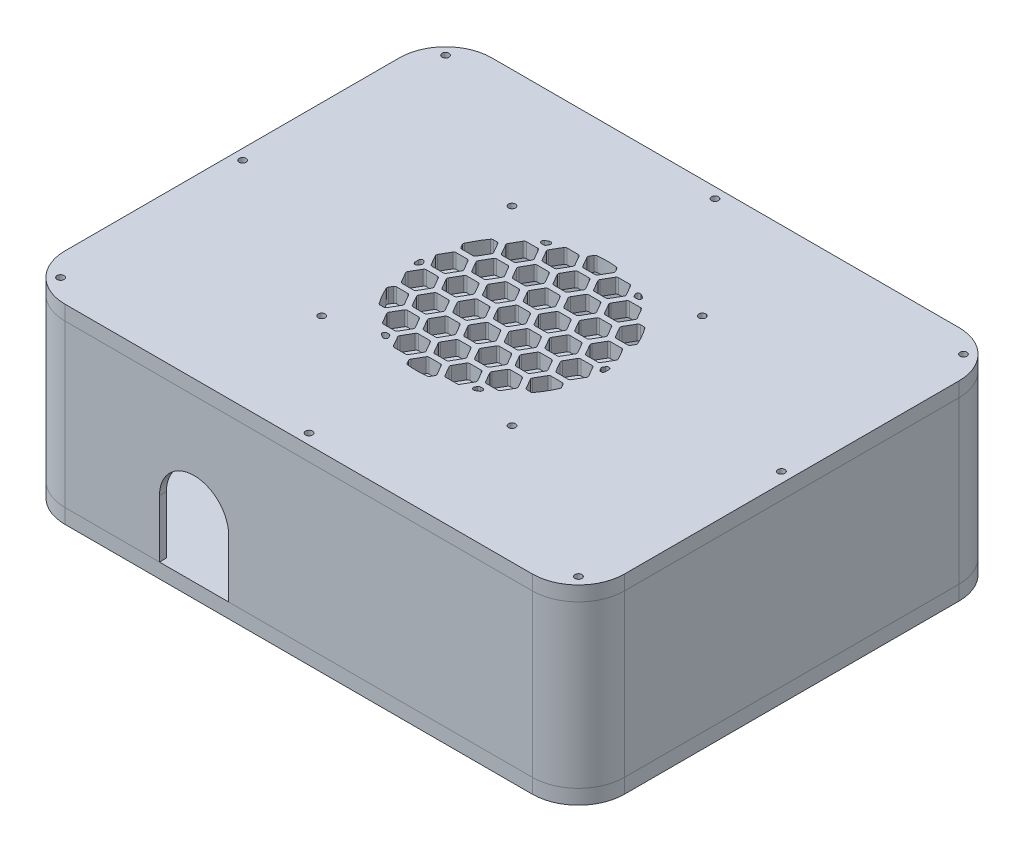
SolidWorks part; units mm, degrees
ref_plane "Front Plane" through (0, 0, 0) normal (0, 0, 1) x (1, 0, 0)
ref_plane "Top Plane" through (0, 0, 0) normal (0, 1, 0) x (1, 0, 0)
ref_plane "Right Plane" through (0, 0, 0) normal (1, 0, 0) x (0, 0, -1)
sketch "Sketch1" plane through (0, 0, 0) normal (0, 1, 0) x (1, 0, 0)
  line L0 (0, 92.5) -> (242.6, 92.5) construction
  line L1 (0, 0) -> (242.6, 0)
  line L2 (0, 0) -> (0, 185)
  line L3 (0, 185) -> (242.6, 185)
  line L4 (242.6, 0) -> (242.6, 185)
  line L6 (89, 170) -> (165.6, 170) construction
  line L7 (89, 170) -> (89, 15) construction
  line L8 (89, 15) -> (165.6, 15) construction
  line L9 (165.6, 170) -> (165.6, 15) construction
  line L10 (15, 106) -> (84, 106) construction
  line L11 (15, 106) -> (15, 15) construction
  line L12 (15, 15) -> (84, 15) construction
  line L13 (84, 106) -> (84, 15) construction
  line L14 (170.6, 127) -> (230.6, 127) construction
  line L15 (170.6, 127) -> (170.6, 15) construction
  line L16 (170.6, 15) -> (230.6, 15) construction
  line L17 (230.6, 127) -> (230.6, 15) construction
  line L22 (15, 170) -> (84, 170) construction
  line L23 (15, 170) -> (15, 121) construction
  line L24 (15, 121) -> (84, 121) construction
  line L25 (84, 170) -> (84, 121) construction
  dimension "D1" = 76.6
  dimension "D2" = 155
  dimension "D3" = 69
  dimension "D4" = 91
  dimension "D5" = 60
  dimension "D6" = 112
  dimension "D7" = 15
  dimension "D8" = 5
  dimension "D9" = 5
  dimension "D10" = 12
  dimension "D11" = 15
  dimension "D12" = 15
  dimension "D13" = 15
extrude "Boss-Extrude1" add sketch "Sketch1" along normal blind 6.35
fillet "Fillet1" radius 20 4 edges at (0, 3.175, -185) (242.6, 3.175, -185) (242.6, 3.175, 0) (0, 3.175, 0)
sketch "Sketch2" plane through (0, 6.35, 0) normal (0, 1, 0) x (1, 0, 0)
  line L0 (89, 170) -> (165.6, 170) construction
  line L1 (92.6, 167) -> (162, 167) construction
  line L2 (92.6, 167) -> (92.6, 25) construction
  line L3 (92.6, 25) -> (162, 25) construction
  line L4 (162, 167) -> (162, 25) construction
  line L5 (170.6, 127) -> (230.6, 127) construction
  line L6 (175.6, 70) -> (225.6, 70) construction
  line L7 (175.6, 70) -> (175.6, 45) construction
  line L8 (175.6, 45) -> (225.6, 45) construction
  line L9 (225.6, 70) -> (225.6, 45) construction
  line L10 (170.6, 15) -> (230.6, 15) construction
  line L11 (15, 170) -> (15, 121) construction
  line L12 (80.996, 125.18) -> (18.004, 125.18) construction
  line L13 (80.996, 125.18) -> (80.996, 165.82) construction
  line L14 (80.996, 165.82) -> (18.004, 165.82) construction
  line L15 (18.004, 125.18) -> (18.004, 165.82) construction
  line L16 (80.996, 125.18) -> (18.004, 165.82) construction
  line L17 (80.996, 165.82) -> (18.004, 125.18) construction
  line L18 (15, 170) -> (84, 170) construction
  circle A0 centre (92.6, 167) radius 1.5
  circle A1 centre (92.6, 25) radius 1.5
  circle A2 centre (162, 25) radius 1.5
  circle A3 centre (162, 167) radius 1.5
  circle A4 centre (175.6, 70) radius 1.5
  circle A5 centre (175.6, 45) radius 1.5
  circle A6 centre (225.6, 70) radius 1.5
  circle A7 centre (225.6, 45) radius 1.5
  circle A8 centre (18.004, 165.82) radius 1.5
  circle A9 centre (80.996, 165.82) radius 1.5
  circle A10 centre (80.996, 125.18) radius 1.5
  circle A11 centre (18.004, 125.18) radius 1.5
  point P6 (127.3, 167)
  point P7 (127.3, 170)
  point P20 (200.6, 70)
  point P23 (200.6, 127)
  point P26 (49.5, 145.5)
  point P34 (15, 145.5)
  point P37 (49.5, 170)
  dimension "D6" = 3
  dimension "D1" = 69.4
  dimension "D2" = 142
  dimension "D3" = 3
  dimension "D4" = 50
  dimension "D5" = 25
  dimension "D7" = 30
  dimension "D8" = 62.992
  dimension "D9" = 40.64
extrude "Cut-Extrude1" cut sketch "Sketch2" against normal through all
sketch "Sketch3" plane through (0, 6.35, 0) normal (0, 1, 0) x (1, 0, 0)
  line L21 (20, 20) -> (9.0398, 9.0398) construction
  line L22 (0, 165) -> (0, 20) construction
  line L23 (6.9185, 11.1612) -> (6.0465, 10.2892)
  line L24 (11.1612, 6.9185) -> (10.2892, 6.0465)
  line L25 (0, 92.5) -> (242.6, 92.5) construction
  line L26 (121.3, 185) -> (121.3, 0) construction
  line L27 (231.4388, 6.9185) -> (232.3108, 6.0465)
  line L28 (235.6815, 11.1612) -> (236.5535, 10.2892)
  line L29 (235.6815, 173.8388) -> (236.5535, 174.7108)
  line L30 (231.4388, 178.0815) -> (232.3108, 178.9535)
  line L31 (11.1612, 178.0815) -> (10.2892, 178.9535)
  line L32 (6.9185, 173.8388) -> (6.0465, 174.7108)
  line L33 (242.6, 20) -> (242.6, 165) construction
  line L34 (20, 0) -> (222.6, 0) construction
  line L35 (222.6, 185) -> (20, 185) construction
  line L36 (20, 20) -> (20, 12.5101) construction
  line L37 (3, 165) -> (3, 20)
  line L38 (20, 3) -> (222.6, 3)
  line L39 (239.6, 20) -> (239.6, 165)
  line L40 (222.6, 182) -> (20, 182)
  line L41 (222.6, 185) -> (20, 185)
  line L42 (0, 165) -> (0, 20)
  line L43 (20, 0) -> (222.6, 0)
  line L44 (242.6, 20) -> (242.6, 165)
  line L45 (222.6, 185) -> (20, 185)
  line L46 (0, 165) -> (0, 20)
  line L47 (20, 0) -> (222.6, 0)
  line L48 (242.6, 20) -> (242.6, 165)
  line L49 (4.5, 95.5) -> (3, 95.5)
  line L50 (3, 95.5) -> (3, 89.5)
  line L51 (3, 89.5) -> (4.5, 89.5)
  line L52 (239.6, 95.5) -> (239.6, 89.5)
  line L53 (238.1, 95.5) -> (239.6, 95.5)
  line L54 (239.6, 89.5) -> (238.1, 89.5)
  line L55 (118.3, 180.5) -> (118.3, 182)
  line L56 (124.3, 180.5) -> (124.3, 182)
  line L57 (118.3, 182) -> (124.3, 182)
  line L58 (118.3, 4.5) -> (118.3, 3)
  line L59 (124.3, 4.5) -> (124.3, 3)
  line L60 (118.3, 3) -> (124.3, 3)
  arc A22 (10.2892, 178.9535) -> (6.0465, 174.7108) centre (20, 165) ccw
  arc A24 (6.0465, 10.2892) -> (10.2892, 6.0465) centre (20, 20) ccw
  arc A26 (232.3108, 6.0465) -> (236.5535, 10.2892) centre (222.6, 20) ccw
  arc A28 (236.5535, 174.7108) -> (232.3108, 178.9535) centre (222.6, 165) ccw
  arc A43 (11.1612, 6.9185) -> (6.9185, 11.1612) centre (9.0398, 9.0398) ccw
  circle A44 centre (9.0398, 9.0398) radius 1.5
  circle A45 centre (233.5602, 9.0398) radius 1.5
  arc A46 (231.4388, 6.9185) -> (235.6815, 11.1612) centre (233.5602, 9.0398) cw
  circle A47 centre (233.5602, 175.9602) radius 1.5
  arc A48 (231.4388, 178.0815) -> (235.6815, 173.8388) centre (233.5602, 175.9602) ccw
  circle A49 centre (9.0398, 175.9602) radius 1.5
  arc A50 (11.1612, 178.0815) -> (6.9185, 173.8388) centre (9.0398, 175.9602) cw
  arc A51 (222.6, 0) -> (242.6, 20) centre (222.6, 20) ccw construction
  arc A52 (0, 20) -> (20, 0) centre (20, 20) ccw construction
  arc A53 (242.6, 165) -> (222.6, 185) centre (222.6, 165) ccw construction
  arc A54 (20, 185) -> (0, 165) centre (20, 165) ccw construction
  arc A55 (3, 20) -> (20, 3) centre (20, 20) ccw
  arc A56 (222.6, 3) -> (239.6, 20) centre (222.6, 20) ccw
  arc A57 (239.6, 165) -> (222.6, 182) centre (222.6, 165) ccw
  arc A58 (20, 182) -> (3, 165) centre (20, 165) ccw
  arc A59 (20, 185) -> (0, 165) centre (20, 165) ccw
  arc A60 (0, 20) -> (20, 0) centre (20, 20) ccw
  arc A61 (222.6, 0) -> (242.6, 20) centre (222.6, 20) ccw
  arc A62 (242.6, 165) -> (222.6, 185) centre (222.6, 165) ccw
  arc A63 (20, 185) -> (0, 165) centre (20, 165) ccw
  arc A64 (0, 20) -> (20, 0) centre (20, 20) ccw
  arc A65 (222.6, 0) -> (242.6, 20) centre (222.6, 20) ccw
  arc A66 (242.6, 165) -> (222.6, 185) centre (222.6, 165) ccw
  arc A67 (4.5, 89.5) -> (4.5, 95.5) centre (4.5, 92.5) ccw
  circle A68 centre (4.5, 92.5) radius 1.5
  arc A69 (238.1, 89.5) -> (238.1, 95.5) centre (238.1, 92.5) cw
  circle A70 centre (238.1, 92.5) radius 1.5
  circle A71 centre (121.3, 180.5) radius 1.5
  arc A72 (118.3, 180.5) -> (124.3, 180.5) centre (121.3, 180.5) ccw
  circle A73 centre (121.3, 4.5) radius 1.5
  arc A74 (118.3, 4.5) -> (124.3, 4.5) centre (121.3, 4.5) cw
  line M50 (222.6, 185) -> (20, 185)
  arc M51 (20, 185) -> (0, 165) centre (20, 165) ccw
  line M52 (0, 165) -> (0, 20)
  arc M53 (0, 20) -> (20, 0) centre (20, 20) ccw
  line M54 (20, 0) -> (222.6, 0)
  arc M55 (222.6, 0) -> (242.6, 20) centre (222.6, 20) ccw
  line M56 (242.6, 20) -> (242.6, 165)
  arc M57 (242.6, 165) -> (222.6, 185) centre (222.6, 165) ccw
  dimension "D3" = 0
  dimension "D4" = 6
  dimension "D5" = 3
  dimension "D1" = 3
  dimension "D7" = 3
  dimension "D6" = 3
  dimension "D2" = 45
extrude "Boss-Extrude2" add sketch "Sketch3" along normal blind 70 separate body contours M57 M50 M51 M52 M53 M54 M55 M56 | A50 L31 A22 A49 L32 | L37 A68 L50 L51 A67 L49 | A24 A44 L24 A43 L23 | A46 L27 A26 A45 L28 | A74 L58 L38 A73 L60 L59 | L39 A70 L52 L53 A69 L54 | L30 A48 L29 A28 A47 | L55 A72 L56 L40 A71 L57 region at (11.1012, 6.35, -11.1012) region at (3.075, 6.35, -91) region at (118.375, 6.35, -3.75) region at (7.0266, 6.35, -175.8543) region at (231.9348, 6.35, -6.5425) region at (119.8, 6.35, -181.925) region at (238.85, 6.35, -89.575) region at (233.4543, 6.35, -177.9734) region at (236.5264, 6.35, -178.9264)
fillet "Fillet5" radius 2 16 edges at (10.2892, 41.35, -178.9535) (6.0465, 41.35, -174.7108) (3, 41.35, -95.5) (3, 41.35, -89.5) (6.0465, 41.35, -10.2892) (10.2892, 41.35, -6.0465) (118.3, 41.35, -3) (124.3, 41.35, -3) (232.3108, 41.35, -6.0465) (236.5535, 41.35, -10.2892) (239.6, 41.35, -89.5) (239.6, 41.35, -95.5) (232.3108, 41.35, -178.9535) (124.3, 41.35, -182) (118.3, 41.35, -182) (236.5535, 41.35, -174.7108)
sketch "Sketch4" plane through (0, 76.35, 0) normal (0, 1, 0) x (1, 0, 0)
  line L4 (0, 165) -> (0, 20)
  line L5 (222.6, 185) -> (20, 185)
  line L6 (242.6, 20) -> (242.6, 165)
  line L7 (20, 0) -> (222.6, 0)
  line L8 (0, 165) -> (0, 20)
  line L9 (222.6, 185) -> (20, 185)
  line L10 (242.6, 20) -> (242.6, 165)
  line L11 (20, 0) -> (222.6, 0)
  arc A4 (20, 185) -> (0, 165) centre (20, 165) ccw
  arc A5 (242.6, 165) -> (222.6, 185) centre (222.6, 165) ccw
  arc A6 (222.6, 0) -> (242.6, 20) centre (222.6, 20) ccw
  arc A7 (0, 20) -> (20, 0) centre (20, 20) ccw
  arc A8 (20, 185) -> (0, 165) centre (20, 165) ccw
  arc A9 (242.6, 165) -> (222.6, 185) centre (222.6, 165) ccw
  arc A10 (222.6, 0) -> (242.6, 20) centre (222.6, 20) ccw
  arc A11 (0, 20) -> (20, 0) centre (20, 20) ccw
  dimension "D1" = 0
extrude "Boss-Extrude4" add sketch "Sketch4" along normal blind 6.35 separate body
sketch "Sketch5" plane through (0, 82.7, 0) normal (0, 1, 0) x (1, 0, 0)
  line L1 (80.05, 133.75) -> (162.55, 133.75) construction
  line L2 (80.05, 133.75) -> (80.05, 51.25) construction
  line L3 (80.05, 51.25) -> (162.55, 51.25) construction
  line L4 (162.55, 133.75) -> (162.55, 51.25) construction
  line L5 (80.05, 133.75) -> (162.55, 51.25) construction
  line L6 (80.05, 51.25) -> (162.55, 133.75) construction
  line L8 (222.6, 185) -> (20, 185) construction
  line L9 (0, 165) -> (0, 20) construction
  circle A0 centre (80.05, 133.75) radius 1.5
  circle A1 centre (80.05, 51.25) radius 1.5
  circle A2 centre (162.55, 51.25) radius 1.5
  circle A3 centre (162.55, 133.75) radius 1.5
  point P0 (121.3, 92.5)
  point P11 (121.3, 185)
  point P12 (0, 92.5)
  dimension "D2" = 3
  dimension "D1" = 82.5
extrude "Cut-Extrude2" cut sketch "Sketch5" against normal through all
sketch "Sketch6" plane through (0, 82.7, 0) normal (0, 1, 0) x (1, 0, 0)
  circle A20 centre (121.3, 4.5) radius 1.5 construction
  circle A21 centre (233.5602, 9.0398) radius 1.5 construction
  circle A22 centre (238.1, 92.5) radius 1.5 construction
  circle A23 centre (233.5602, 175.9602) radius 1.5 construction
  circle A24 centre (121.3, 180.5) radius 1.5 construction
  circle A25 centre (9.0398, 175.9602) radius 1.5 construction
  circle A26 centre (4.5, 92.5) radius 1.5 construction
  circle A27 centre (9.0398, 9.0398) radius 1.5 construction
  circle A28 centre (121.3, 4.5) radius 1.5
  circle A29 centre (233.5602, 9.0398) radius 1.5
  circle A30 centre (238.1, 92.5) radius 1.5
  circle A31 centre (233.5602, 175.9602) radius 1.5
  circle A32 centre (121.3, 180.5) radius 1.5
  circle A33 centre (9.0398, 175.9602) radius 1.5
  circle A34 centre (4.5, 92.5) radius 1.5
  circle A35 centre (9.0398, 9.0398) radius 1.5
extrude "Cut-Extrude3" cut sketch "Sketch6" against normal through all
sketch "Sketch7" plane through (0, 82.7, 0) normal (0, 1, 0) x (1, 0, 0)
  line L0 (80.05, 133.75) -> (162.55, 133.75) construction
  line L1 (80.05, 133.75) -> (80.05, 51.25) construction
  line L2 (80.05, 51.25) -> (162.55, 51.25) construction
  line L3 (162.55, 133.75) -> (162.55, 51.25) construction
  line L4 (80.05, 133.75) -> (162.55, 133.75) construction
  line L5 (80.05, 133.75) -> (80.05, 51.25) construction
  line L6 (80.05, 51.25) -> (162.55, 51.25) construction
  line L7 (162.55, 133.75) -> (162.55, 51.25) construction
  line L8 (157.7952, 117.0346) -> (151.7952, 117.0346)
  line L9 (124.3, 97.6962) -> (118.3, 97.6962)
  line L10 (118.3, 97.6962) -> (115.3, 92.5)
  line L11 (115.3, 92.5) -> (118.3, 87.3038)
  line L12 (118.3, 87.3038) -> (124.3, 87.3038)
  line L13 (124.3, 87.3038) -> (127.3, 92.5)
  line L14 (127.3, 92.5) -> (124.3, 97.6962)
  line L15 (138.4651, 98.9462) -> (135.4651, 104.1423)
  line L16 (135.4651, 104.1423) -> (129.4651, 104.1423)
  line L17 (129.4651, 104.1423) -> (126.4651, 98.9462)
  line L18 (126.4651, 98.9462) -> (129.4651, 93.75)
  line L19 (129.4651, 93.75) -> (135.4651, 93.75)
  line L20 (135.4651, 93.75) -> (138.4651, 98.9462)
  line L21 (127.3, 105.3923) -> (124.3, 110.5885)
  line L22 (124.3, 110.5885) -> (118.3, 110.5885)
  line L23 (118.3, 110.5885) -> (115.3, 105.3923)
  line L24 (115.3, 105.3923) -> (118.3, 100.1962)
  line L25 (118.3, 100.1962) -> (124.3, 100.1962)
  line L26 (124.3, 100.1962) -> (127.3, 105.3923)
  line L27 (135.4651, 117.0346) -> (129.4651, 117.0346)
  line L28 (129.4651, 117.0346) -> (126.4651, 111.8385)
  line L29 (126.4651, 111.8385) -> (129.4651, 106.6423)
  line L30 (129.4651, 106.6423) -> (135.4651, 106.6423)
  line L31 (135.4651, 106.6423) -> (138.4651, 111.8385)
  line L32 (138.4651, 111.8385) -> (135.4651, 117.0346)
  line L33 (151.7952, 117.0346) -> (148.7952, 111.8385)
  line L34 (148.7952, 111.8385) -> (151.7952, 106.6423)
  line L35 (151.7952, 106.6423) -> (157.7952, 106.6423)
  line L36 (157.7952, 106.6423) -> (160.7952, 111.8385)
  line L37 (160.7952, 111.8385) -> (157.7952, 117.0346)
  line L38 (149.6301, 105.3923) -> (146.6301, 110.5885)
  line L39 (146.6301, 110.5885) -> (140.6301, 110.5885)
  line L40 (140.6301, 110.5885) -> (137.6301, 105.3923)
  line L41 (137.6301, 105.3923) -> (140.6301, 100.1962)
  line L42 (140.6301, 100.1962) -> (146.6301, 100.1962)
  line L43 (146.6301, 100.1962) -> (149.6301, 105.3923)
  line L44 (146.6301, 97.6962) -> (140.6301, 97.6962)
  line L45 (140.6301, 97.6962) -> (137.6301, 92.5)
  line L46 (137.6301, 92.5) -> (140.6301, 87.3038)
  line L47 (140.6301, 87.3038) -> (146.6301, 87.3038)
  line L48 (146.6301, 87.3038) -> (149.6301, 92.5)
  line L49 (149.6301, 92.5) -> (146.6301, 97.6962)
  line L50 (160.7952, 98.9462) -> (157.7952, 104.1423)
  line L51 (157.7952, 104.1423) -> (151.7952, 104.1423)
  line L52 (151.7952, 104.1423) -> (148.7952, 98.9462)
  line L53 (148.7952, 98.9462) -> (151.7952, 93.75)
  line L54 (151.7952, 93.75) -> (157.7952, 93.75)
  line L55 (157.7952, 93.75) -> (160.7952, 98.9462)
  line L56 (180.1253, 117.0346) -> (174.1253, 117.0346)
  line L57 (174.1253, 117.0346) -> (171.1253, 111.8385)
  line L58 (171.1253, 111.8385) -> (174.1253, 106.6423)
  line L59 (174.1253, 106.6423) -> (180.1253, 106.6423)
  line L60 (180.1253, 106.6423) -> (183.1253, 111.8385)
  line L61 (183.1253, 111.8385) -> (180.1253, 117.0346)
  line L62 (171.9603, 105.3923) -> (168.9603, 110.5885)
  line L63 (168.9603, 110.5885) -> (162.9603, 110.5885)
  line L64 (162.9603, 110.5885) -> (159.9603, 105.3923)
  line L65 (159.9603, 105.3923) -> (162.9603, 100.1962)
  line L66 (162.9603, 100.1962) -> (168.9603, 100.1962)
  line L67 (168.9603, 100.1962) -> (171.9603, 105.3923)
  line L68 (168.9603, 97.6962) -> (162.9603, 97.6962)
  line L69 (162.9603, 97.6962) -> (159.9603, 92.5)
  line L70 (159.9603, 92.5) -> (162.9603, 87.3038)
  line L71 (162.9603, 87.3038) -> (168.9603, 87.3038)
  line L72 (168.9603, 87.3038) -> (171.9603, 92.5)
  line L73 (171.9603, 92.5) -> (168.9603, 97.6962)
  line L74 (183.1253, 98.9462) -> (180.1253, 104.1423)
  line L75 (180.1253, 104.1423) -> (174.1253, 104.1423)
  line L76 (174.1253, 104.1423) -> (171.1253, 98.9462)
  line L77 (171.1253, 98.9462) -> (174.1253, 93.75)
  line L78 (174.1253, 93.75) -> (180.1253, 93.75)
  line L79 (180.1253, 93.75) -> (183.1253, 98.9462)
  line L80 (157.7952, 142.8192) -> (151.7952, 142.8192)
  line L81 (151.7952, 142.8192) -> (148.7952, 137.6231)
  line L82 (148.7952, 137.6231) -> (151.7952, 132.4269)
  line L83 (151.7952, 132.4269) -> (157.7952, 132.4269)
  line L84 (157.7952, 132.4269) -> (160.7952, 137.6231)
  line L85 (160.7952, 137.6231) -> (157.7952, 142.8192)
  line L86 (149.6301, 131.1769) -> (146.6301, 136.3731)
  line L87 (146.6301, 136.3731) -> (140.6301, 136.3731)
  line L88 (140.6301, 136.3731) -> (137.6301, 131.1769)
  line L89 (137.6301, 131.1769) -> (140.6301, 125.9808)
  line L90 (140.6301, 125.9808) -> (146.6301, 125.9808)
  line L91 (146.6301, 125.9808) -> (149.6301, 131.1769)
  line L92 (146.6301, 123.4808) -> (140.6301, 123.4808)
  line L93 (140.6301, 123.4808) -> (137.6301, 118.2846)
  line L94 (137.6301, 118.2846) -> (140.6301, 113.0885)
  line L95 (140.6301, 113.0885) -> (146.6301, 113.0885)
  line L96 (146.6301, 113.0885) -> (149.6301, 118.2846)
  line L97 (149.6301, 118.2846) -> (146.6301, 123.4808)
  line L98 (160.7952, 124.7308) -> (157.7952, 129.9269)
  line L99 (157.7952, 129.9269) -> (151.7952, 129.9269)
  line L100 (151.7952, 129.9269) -> (148.7952, 124.7308)
  line L101 (148.7952, 124.7308) -> (151.7952, 119.5346)
  line L102 (151.7952, 119.5346) -> (157.7952, 119.5346)
  line L103 (157.7952, 119.5346) -> (160.7952, 124.7308)
  line L104 (180.1253, 142.8192) -> (174.1253, 142.8192)
  line L105 (174.1253, 142.8192) -> (171.1253, 137.6231)
  line L106 (171.1253, 137.6231) -> (174.1253, 132.4269)
  line L107 (174.1253, 132.4269) -> (180.1253, 132.4269)
  line L108 (180.1253, 132.4269) -> (183.1253, 137.6231)
  line L109 (183.1253, 137.6231) -> (180.1253, 142.8192)
  line L110 (171.9603, 131.1769) -> (168.9603, 136.3731)
  line L111 (168.9603, 136.3731) -> (162.9603, 136.3731)
  line L112 (162.9603, 136.3731) -> (159.9603, 131.1769)
  line L113 (159.9603, 131.1769) -> (162.9603, 125.9808)
  line L114 (162.9603, 125.9808) -> (168.9603, 125.9808)
  line L115 (168.9603, 125.9808) -> (171.9603, 131.1769)
  line L116 (168.9603, 123.4808) -> (162.9603, 123.4808)
  line L117 (162.9603, 123.4808) -> (159.9603, 118.2846)
  line L118 (159.9603, 118.2846) -> (162.9603, 113.0885)
  line L119 (162.9603, 113.0885) -> (168.9603, 113.0885)
  line L120 (168.9603, 113.0885) -> (171.9603, 118.2846)
  line L121 (171.9603, 118.2846) -> (168.9603, 123.4808)
  line L122 (183.1253, 124.7308) -> (180.1253, 129.9269)
  line L123 (180.1253, 129.9269) -> (174.1253, 129.9269)
  line L124 (174.1253, 129.9269) -> (171.1253, 124.7308)
  line L125 (171.1253, 124.7308) -> (174.1253, 119.5346)
  line L126 (174.1253, 119.5346) -> (180.1253, 119.5346)
  line L127 (180.1253, 119.5346) -> (183.1253, 124.7308)
  line L128 (135.4651, 142.8192) -> (129.4651, 142.8192)
  line L129 (129.4651, 142.8192) -> (126.4651, 137.6231)
  line L130 (126.4651, 137.6231) -> (129.4651, 132.4269)
  line L131 (129.4651, 132.4269) -> (135.4651, 132.4269)
  line L132 (135.4651, 132.4269) -> (138.4651, 137.6231)
  line L133 (138.4651, 137.6231) -> (135.4651, 142.8192)
  line L134 (127.3, 131.1769) -> (124.3, 136.3731)
  line L135 (124.3, 136.3731) -> (118.3, 136.3731)
  line L136 (118.3, 136.3731) -> (115.3, 131.1769)
  line L137 (115.3, 131.1769) -> (118.3, 125.9808)
  line L138 (118.3, 125.9808) -> (124.3, 125.9808)
  line L139 (124.3, 125.9808) -> (127.3, 131.1769)
  line L140 (124.3, 123.4808) -> (118.3, 123.4808)
  line L141 (118.3, 123.4808) -> (115.3, 118.2846)
  line L142 (115.3, 118.2846) -> (118.3, 113.0885)
  line L143 (118.3, 113.0885) -> (124.3, 113.0885)
  line L144 (124.3, 113.0885) -> (127.3, 118.2846)
  line L145 (127.3, 118.2846) -> (124.3, 123.4808)
  line L146 (138.4651, 124.7308) -> (135.4651, 129.9269)
  line L147 (135.4651, 129.9269) -> (129.4651, 129.9269)
  line L148 (129.4651, 129.9269) -> (126.4651, 124.7308)
  line L149 (126.4651, 124.7308) -> (129.4651, 119.5346)
  line L150 (129.4651, 119.5346) -> (135.4651, 119.5346)
  line L151 (135.4651, 119.5346) -> (138.4651, 124.7308)
  line L152 (124.3, 84.8038) -> (118.3, 84.8038)
  line L153 (118.3, 84.8038) -> (115.3, 79.6077)
  line L154 (115.3, 79.6077) -> (118.3, 74.4115)
  line L155 (118.3, 74.4115) -> (124.3, 74.4115)
  line L156 (124.3, 74.4115) -> (127.3, 79.6077)
  line L157 (127.3, 79.6077) -> (124.3, 84.8038)
  line L158 (138.4651, 86.0538) -> (135.4651, 91.25)
  line L159 (135.4651, 91.25) -> (129.4651, 91.25)
  line L160 (129.4651, 91.25) -> (126.4651, 86.0538)
  line L161 (126.4651, 86.0538) -> (129.4651, 80.8577)
  line L162 (129.4651, 80.8577) -> (135.4651, 80.8577)
  line L163 (135.4651, 80.8577) -> (138.4651, 86.0538)
  line L164 (160.7952, 86.0538) -> (157.7952, 91.25)
  line L165 (157.7952, 91.25) -> (151.7952, 91.25)
  line L166 (151.7952, 91.25) -> (148.7952, 86.0538)
  line L167 (148.7952, 86.0538) -> (151.7952, 80.8577)
  line L168 (151.7952, 80.8577) -> (157.7952, 80.8577)
  line L169 (157.7952, 80.8577) -> (160.7952, 86.0538)
  line L170 (168.9603, 84.8038) -> (162.9603, 84.8038)
  line L171 (162.9603, 84.8038) -> (159.9603, 79.6077)
  line L172 (159.9603, 79.6077) -> (162.9603, 74.4115)
  line L173 (162.9603, 74.4115) -> (168.9603, 74.4115)
  line L174 (168.9603, 74.4115) -> (171.9603, 79.6077)
  line L175 (171.9603, 79.6077) -> (168.9603, 84.8038)
  line L176 (146.6301, 84.8038) -> (140.6301, 84.8038)
  line L177 (140.6301, 84.8038) -> (137.6301, 79.6077)
  line L178 (137.6301, 79.6077) -> (140.6301, 74.4115)
  line L179 (140.6301, 74.4115) -> (146.6301, 74.4115)
  line L180 (146.6301, 74.4115) -> (149.6301, 79.6077)
  line L181 (149.6301, 79.6077) -> (146.6301, 84.8038)
  line L182 (124.3, 71.9115) -> (118.3, 71.9115)
  line L183 (118.3, 71.9115) -> (115.3, 66.7154)
  line L184 (115.3, 66.7154) -> (118.3, 61.5192)
  line L185 (118.3, 61.5192) -> (124.3, 61.5192)
  line L186 (124.3, 61.5192) -> (127.3, 66.7154)
  line L187 (127.3, 66.7154) -> (124.3, 71.9115)
  line L188 (138.4651, 73.1615) -> (135.4651, 78.3577)
  line L189 (135.4651, 78.3577) -> (129.4651, 78.3577)
  line L190 (129.4651, 78.3577) -> (126.4651, 73.1615)
  line L191 (126.4651, 73.1615) -> (129.4651, 67.9654)
  line L192 (129.4651, 67.9654) -> (135.4651, 67.9654)
  line L193 (135.4651, 67.9654) -> (138.4651, 73.1615)
  line L194 (160.7952, 73.1615) -> (157.7952, 78.3577)
  line L195 (157.7952, 78.3577) -> (151.7952, 78.3577)
  line L196 (151.7952, 78.3577) -> (148.7952, 73.1615)
  line L197 (148.7952, 73.1615) -> (151.7952, 67.9654)
  line L198 (151.7952, 67.9654) -> (157.7952, 67.9654)
  line L199 (157.7952, 67.9654) -> (160.7952, 73.1615)
  line L200 (168.9603, 71.9115) -> (162.9603, 71.9115)
  line L201 (162.9603, 71.9115) -> (159.9603, 66.7154)
  line L202 (159.9603, 66.7154) -> (162.9603, 61.5192)
  line L203 (162.9603, 61.5192) -> (168.9603, 61.5192)
  line L204 (168.9603, 61.5192) -> (171.9603, 66.7154)
  line L205 (171.9603, 66.7154) -> (168.9603, 71.9115)
  line L206 (146.6301, 71.9115) -> (140.6301, 71.9115)
  line L207 (140.6301, 71.9115) -> (137.6301, 66.7154)
  line L208 (137.6301, 66.7154) -> (140.6301, 61.5192)
  line L209 (140.6301, 61.5192) -> (146.6301, 61.5192)
  line L210 (146.6301, 61.5192) -> (149.6301, 66.7154)
  line L211 (149.6301, 66.7154) -> (146.6301, 71.9115)
  line L212 (124.3, 59.0192) -> (118.3, 59.0192)
  line L213 (118.3, 59.0192) -> (115.3, 53.8231)
  line L214 (115.3, 53.8231) -> (118.3, 48.6269)
  line L215 (118.3, 48.6269) -> (124.3, 48.6269)
  line L216 (124.3, 48.6269) -> (127.3, 53.8231)
  line L217 (127.3, 53.8231) -> (124.3, 59.0192)
  line L218 (138.4651, 60.2692) -> (135.4651, 65.4654)
  line L219 (135.4651, 65.4654) -> (129.4651, 65.4654)
  line L220 (129.4651, 65.4654) -> (126.4651, 60.2692)
  line L221 (126.4651, 60.2692) -> (129.4651, 55.0731)
  line L222 (129.4651, 55.0731) -> (135.4651, 55.0731)
  line L223 (135.4651, 55.0731) -> (138.4651, 60.2692)
  line L224 (160.7952, 60.2692) -> (157.7952, 65.4654)
  line L225 (157.7952, 65.4654) -> (151.7952, 65.4654)
  line L226 (151.7952, 65.4654) -> (148.7952, 60.2692)
  line L227 (148.7952, 60.2692) -> (151.7952, 55.0731)
  line L228 (151.7952, 55.0731) -> (157.7952, 55.0731)
  line L229 (157.7952, 55.0731) -> (160.7952, 60.2692)
  line L230 (168.9603, 59.0192) -> (162.9603, 59.0192)
  line L231 (162.9603, 59.0192) -> (159.9603, 53.8231)
  line L232 (159.9603, 53.8231) -> (162.9603, 48.6269)
  line L233 (162.9603, 48.6269) -> (168.9603, 48.6269)
  line L234 (168.9603, 48.6269) -> (171.9603, 53.8231)
  line L235 (171.9603, 53.8231) -> (168.9603, 59.0192)
  line L236 (146.6301, 59.0192) -> (140.6301, 59.0192)
  line L237 (140.6301, 59.0192) -> (137.6301, 53.8231)
  line L238 (137.6301, 53.8231) -> (140.6301, 48.6269)
  line L239 (140.6301, 48.6269) -> (146.6301, 48.6269)
  line L240 (146.6301, 48.6269) -> (149.6301, 53.8231)
  line L241 (149.6301, 53.8231) -> (146.6301, 59.0192)
  line L242 (124.3, 46.1269) -> (118.3, 46.1269)
  line L243 (118.3, 46.1269) -> (115.3, 40.9308)
  line L244 (115.3, 40.9308) -> (118.3, 35.7346)
  line L245 (118.3, 35.7346) -> (124.3, 35.7346)
  line L246 (124.3, 35.7346) -> (127.3, 40.9308)
  line L247 (127.3, 40.9308) -> (124.3, 46.1269)
  line L248 (138.4651, 47.3769) -> (135.4651, 52.5731)
  line L249 (135.4651, 52.5731) -> (129.4651, 52.5731)
  line L250 (129.4651, 52.5731) -> (126.4651, 47.3769)
  line L251 (126.4651, 47.3769) -> (129.4651, 42.1808)
  line L252 (129.4651, 42.1808) -> (135.4651, 42.1808)
  line L253 (135.4651, 42.1808) -> (138.4651, 47.3769)
  line L254 (160.7952, 47.3769) -> (157.7952, 52.5731)
  line L255 (157.7952, 52.5731) -> (151.7952, 52.5731)
  line L256 (151.7952, 52.5731) -> (148.7952, 47.3769)
  line L257 (148.7952, 47.3769) -> (151.7952, 42.1808)
  line L258 (151.7952, 42.1808) -> (157.7952, 42.1808)
  line L259 (157.7952, 42.1808) -> (160.7952, 47.3769)
  line L260 (168.9603, 46.1269) -> (162.9603, 46.1269)
  line L261 (162.9603, 46.1269) -> (159.9603, 40.9308)
  line L262 (159.9603, 40.9308) -> (162.9603, 35.7346)
  line L263 (162.9603, 35.7346) -> (168.9603, 35.7346)
  line L264 (168.9603, 35.7346) -> (171.9603, 40.9308)
  line L265 (171.9603, 40.9308) -> (168.9603, 46.1269)
  line L266 (146.6301, 46.1269) -> (140.6301, 46.1269)
  line L267 (140.6301, 46.1269) -> (137.6301, 40.9308)
  line L268 (137.6301, 40.9308) -> (140.6301, 35.7346)
  line L269 (140.6301, 35.7346) -> (146.6301, 35.7346)
  line L270 (146.6301, 35.7346) -> (149.6301, 40.9308)
  line L271 (149.6301, 40.9308) -> (146.6301, 46.1269)
  line L272 (104.9699, 131.1769) -> (101.9699, 136.3731)
  line L273 (101.9699, 136.3731) -> (95.9699, 136.3731)
  line L274 (95.9699, 136.3731) -> (92.9699, 131.1769)
  line L275 (92.9699, 131.1769) -> (95.9699, 125.9808)
  line L276 (95.9699, 125.9808) -> (101.9699, 125.9808)
  line L277 (101.9699, 125.9808) -> (104.9699, 131.1769)
  line L278 (101.9699, 123.4808) -> (95.9699, 123.4808)
  line L279 (95.9699, 123.4808) -> (92.9699, 118.2846)
  line L280 (92.9699, 118.2846) -> (95.9699, 113.0885)
  line L281 (95.9699, 113.0885) -> (101.9699, 113.0885)
  line L282 (101.9699, 113.0885) -> (104.9699, 118.2846)
  line L283 (104.9699, 118.2846) -> (101.9699, 123.4808)
  line L284 (101.9699, 84.8038) -> (95.9699, 84.8038)
  line L285 (95.9699, 84.8038) -> (92.9699, 79.6077)
  line L286 (92.9699, 79.6077) -> (95.9699, 74.4115)
  line L287 (95.9699, 74.4115) -> (101.9699, 74.4115)
  line L288 (101.9699, 74.4115) -> (104.9699, 79.6077)
  line L289 (104.9699, 79.6077) -> (101.9699, 84.8038)
  line L290 (101.9699, 71.9115) -> (95.9699, 71.9115)
  line L291 (95.9699, 71.9115) -> (92.9699, 66.7154)
  line L292 (92.9699, 66.7154) -> (95.9699, 61.5192)
  line L293 (95.9699, 61.5192) -> (101.9699, 61.5192)
  line L294 (101.9699, 61.5192) -> (104.9699, 66.7154)
  line L295 (104.9699, 66.7154) -> (101.9699, 71.9115)
  line L296 (101.9699, 59.0192) -> (95.9699, 59.0192)
  line L297 (95.9699, 59.0192) -> (92.9699, 53.8231)
  line L298 (92.9699, 53.8231) -> (95.9699, 48.6269)
  line L299 (95.9699, 48.6269) -> (101.9699, 48.6269)
  line L300 (101.9699, 48.6269) -> (104.9699, 53.8231)
  line L301 (104.9699, 53.8231) -> (101.9699, 59.0192)
  line L302 (116.1349, 60.2692) -> (113.1349, 65.4654)
  line L303 (113.1349, 65.4654) -> (107.1349, 65.4654)
  line L304 (107.1349, 65.4654) -> (104.1349, 60.2692)
  line L305 (104.1349, 60.2692) -> (107.1349, 55.0731)
  line L306 (107.1349, 55.0731) -> (113.1349, 55.0731)
  line L307 (113.1349, 55.0731) -> (116.1349, 60.2692)
  line L308 (116.1349, 73.1615) -> (113.1349, 78.3577)
  line L309 (113.1349, 78.3577) -> (107.1349, 78.3577)
  line L310 (107.1349, 78.3577) -> (104.1349, 73.1615)
  line L311 (104.1349, 73.1615) -> (107.1349, 67.9654)
  line L312 (107.1349, 67.9654) -> (113.1349, 67.9654)
  line L313 (113.1349, 67.9654) -> (116.1349, 73.1615)
  line L314 (101.9699, 97.6962) -> (95.9699, 97.6962)
  line L315 (95.9699, 97.6962) -> (92.9699, 92.5)
  line L316 (92.9699, 92.5) -> (95.9699, 87.3038)
  line L317 (95.9699, 87.3038) -> (101.9699, 87.3038)
  line L318 (101.9699, 87.3038) -> (104.9699, 92.5)
  line L319 (104.9699, 92.5) -> (101.9699, 97.6962)
  line L320 (116.1349, 86.0538) -> (113.1349, 91.25)
  line L321 (113.1349, 91.25) -> (107.1349, 91.25)
  line L322 (107.1349, 91.25) -> (104.1349, 86.0538)
  line L323 (104.1349, 86.0538) -> (107.1349, 80.8577)
  line L324 (107.1349, 80.8577) -> (113.1349, 80.8577)
  line L325 (113.1349, 80.8577) -> (116.1349, 86.0538)
  line L326 (116.1349, 98.9462) -> (113.1349, 104.1423)
  line L327 (113.1349, 104.1423) -> (107.1349, 104.1423)
  line L328 (107.1349, 104.1423) -> (104.1349, 98.9462)
  line L329 (104.1349, 98.9462) -> (107.1349, 93.75)
  line L330 (107.1349, 93.75) -> (113.1349, 93.75)
  line L331 (113.1349, 93.75) -> (116.1349, 98.9462)
  line L332 (104.9699, 105.3923) -> (101.9699, 110.5885)
  line L333 (101.9699, 110.5885) -> (95.9699, 110.5885)
  line L334 (95.9699, 110.5885) -> (92.9699, 105.3923)
  line L335 (92.9699, 105.3923) -> (95.9699, 100.1962)
  line L336 (95.9699, 100.1962) -> (101.9699, 100.1962)
  line L337 (101.9699, 100.1962) -> (104.9699, 105.3923)
  line L338 (113.1349, 117.0346) -> (107.1349, 117.0346)
  line L339 (107.1349, 117.0346) -> (104.1349, 111.8385)
  line L340 (104.1349, 111.8385) -> (107.1349, 106.6423)
  line L341 (107.1349, 106.6423) -> (113.1349, 106.6423)
  line L342 (113.1349, 106.6423) -> (116.1349, 111.8385)
  line L343 (116.1349, 111.8385) -> (113.1349, 117.0346)
  line L344 (116.1349, 124.7308) -> (113.1349, 129.9269)
  line L345 (113.1349, 129.9269) -> (107.1349, 129.9269)
  line L346 (107.1349, 129.9269) -> (104.1349, 124.7308)
  line L347 (104.1349, 124.7308) -> (107.1349, 119.5346)
  line L348 (107.1349, 119.5346) -> (113.1349, 119.5346)
  line L349 (113.1349, 119.5346) -> (116.1349, 124.7308)
  line L350 (116.1349, 47.3769) -> (113.1349, 52.5731)
  line L351 (113.1349, 52.5731) -> (107.1349, 52.5731)
  line L352 (107.1349, 52.5731) -> (104.1349, 47.3769)
  line L353 (104.1349, 47.3769) -> (107.1349, 42.1808)
  line L354 (107.1349, 42.1808) -> (113.1349, 42.1808)
  line L355 (113.1349, 42.1808) -> (116.1349, 47.3769)
  line L356 (82.6397, 131.1769) -> (79.6397, 136.3731)
  line L357 (79.6397, 136.3731) -> (73.6397, 136.3731)
  line L358 (73.6397, 136.3731) -> (70.6397, 131.1769)
  line L359 (70.6397, 131.1769) -> (73.6397, 125.9808)
  line L360 (73.6397, 125.9808) -> (79.6397, 125.9808)
  line L361 (79.6397, 125.9808) -> (82.6397, 131.1769)
  line L362 (79.6397, 123.4808) -> (73.6397, 123.4808)
  line L363 (73.6397, 123.4808) -> (70.6397, 118.2846)
  line L364 (70.6397, 118.2846) -> (73.6397, 113.0885)
  line L365 (73.6397, 113.0885) -> (79.6397, 113.0885)
  line L366 (79.6397, 113.0885) -> (82.6397, 118.2846)
  line L367 (82.6397, 118.2846) -> (79.6397, 123.4808)
  line L368 (79.6397, 84.8038) -> (73.6397, 84.8038)
  line L369 (73.6397, 84.8038) -> (70.6397, 79.6077)
  line L370 (70.6397, 79.6077) -> (73.6397, 74.4115)
  line L371 (73.6397, 74.4115) -> (79.6397, 74.4115)
  line L372 (79.6397, 74.4115) -> (82.6397, 79.6077)
  line L373 (82.6397, 79.6077) -> (79.6397, 84.8038)
  line L374 (79.6397, 71.9115) -> (73.6397, 71.9115)
  line L375 (73.6397, 71.9115) -> (70.6397, 66.7154)
  line L376 (70.6397, 66.7154) -> (73.6397, 61.5192)
  line L377 (73.6397, 61.5192) -> (79.6397, 61.5192)
  line L378 (79.6397, 61.5192) -> (82.6397, 66.7154)
  line L379 (82.6397, 66.7154) -> (79.6397, 71.9115)
  line L380 (79.6397, 59.0192) -> (73.6397, 59.0192)
  line L381 (73.6397, 59.0192) -> (70.6397, 53.8231)
  line L382 (70.6397, 53.8231) -> (73.6397, 48.6269)
  line L383 (73.6397, 48.6269) -> (79.6397, 48.6269)
  line L384 (79.6397, 48.6269) -> (82.6397, 53.8231)
  line L385 (82.6397, 53.8231) -> (79.6397, 59.0192)
  line L386 (93.8048, 60.2692) -> (90.8048, 65.4654)
  line L387 (90.8048, 65.4654) -> (84.8048, 65.4654)
  line L388 (84.8048, 65.4654) -> (81.8048, 60.2692)
  line L389 (81.8048, 60.2692) -> (84.8048, 55.0731)
  line L390 (84.8048, 55.0731) -> (90.8048, 55.0731)
  line L391 (90.8048, 55.0731) -> (93.8048, 60.2692)
  line L392 (93.8048, 73.1615) -> (90.8048, 78.3577)
  line L393 (90.8048, 78.3577) -> (84.8048, 78.3577)
  line L394 (84.8048, 78.3577) -> (81.8048, 73.1615)
  line L395 (81.8048, 73.1615) -> (84.8048, 67.9654)
  line L396 (84.8048, 67.9654) -> (90.8048, 67.9654)
  line L397 (90.8048, 67.9654) -> (93.8048, 73.1615)
  line L398 (79.6397, 97.6962) -> (73.6397, 97.6962)
  line L399 (73.6397, 97.6962) -> (70.6397, 92.5)
  line L400 (70.6397, 92.5) -> (73.6397, 87.3038)
  line L401 (73.6397, 87.3038) -> (79.6397, 87.3038)
  line L402 (79.6397, 87.3038) -> (82.6397, 92.5)
  line L403 (82.6397, 92.5) -> (79.6397, 97.6962)
  line L404 (93.8048, 86.0538) -> (90.8048, 91.25)
  line L405 (90.8048, 91.25) -> (84.8048, 91.25)
  line L406 (84.8048, 91.25) -> (81.8048, 86.0538)
  line L407 (81.8048, 86.0538) -> (84.8048, 80.8577)
  line L408 (84.8048, 80.8577) -> (90.8048, 80.8577)
  line L409 (90.8048, 80.8577) -> (93.8048, 86.0538)
  line L410 (93.8048, 98.9462) -> (90.8048, 104.1423)
  line L411 (90.8048, 104.1423) -> (84.8048, 104.1423)
  line L412 (84.8048, 104.1423) -> (81.8048, 98.9462)
  line L413 (81.8048, 98.9462) -> (84.8048, 93.75)
  line L414 (84.8048, 93.75) -> (90.8048, 93.75)
  line L415 (90.8048, 93.75) -> (93.8048, 98.9462)
  line L416 (82.6397, 105.3923) -> (79.6397, 110.5885)
  line L417 (79.6397, 110.5885) -> (73.6397, 110.5885)
  line L418 (73.6397, 110.5885) -> (70.6397, 105.3923)
  line L419 (70.6397, 105.3923) -> (73.6397, 100.1962)
  line L420 (73.6397, 100.1962) -> (79.6397, 100.1962)
  line L421 (79.6397, 100.1962) -> (82.6397, 105.3923)
  line L422 (90.8048, 117.0346) -> (84.8048, 117.0346)
  line L423 (84.8048, 117.0346) -> (81.8048, 111.8385)
  line L424 (81.8048, 111.8385) -> (84.8048, 106.6423)
  line L425 (84.8048, 106.6423) -> (90.8048, 106.6423)
  line L426 (90.8048, 106.6423) -> (93.8048, 111.8385)
  line L427 (93.8048, 111.8385) -> (90.8048, 117.0346)
  line L428 (93.8048, 124.7308) -> (90.8048, 129.9269)
  line L429 (90.8048, 129.9269) -> (84.8048, 129.9269)
  line L430 (84.8048, 129.9269) -> (81.8048, 124.7308)
  line L431 (81.8048, 124.7308) -> (84.8048, 119.5346)
  line L432 (84.8048, 119.5346) -> (90.8048, 119.5346)
  line L433 (90.8048, 119.5346) -> (93.8048, 124.7308)
  line L434 (93.8048, 47.3769) -> (90.8048, 52.5731)
  line L435 (90.8048, 52.5731) -> (84.8048, 52.5731)
  line L436 (84.8048, 52.5731) -> (81.8048, 47.3769)
  line L437 (81.8048, 47.3769) -> (84.8048, 42.1808)
  line L438 (84.8048, 42.1808) -> (90.8048, 42.1808)
  line L439 (90.8048, 42.1808) -> (93.8048, 47.3769)
  line L440 (116.1349, 137.6231) -> (113.1349, 142.8192)
  line L441 (113.1349, 142.8192) -> (107.1349, 142.8192)
  line L442 (107.1349, 142.8192) -> (104.1349, 137.6231)
  line L443 (104.1349, 137.6231) -> (107.1349, 132.4269)
  line L444 (107.1349, 132.4269) -> (113.1349, 132.4269)
  line L445 (113.1349, 132.4269) -> (116.1349, 137.6231)
  circle A0 centre (121.3, 92.5) radius 41.25
  circle A4 centre (121.3, 92.5) radius 5.1962 construction
  circle A5 centre (132.4651, 98.9462) radius 5.1962 construction
  circle A6 centre (121.3, 105.3923) radius 5.1962 construction
  circle A7 centre (132.4651, 111.8385) radius 5.1962 construction
  point P15 (125.8, 107.9904)
  dimension "D1" = 6
  dimension "D2" = 2.5
  dimension "D3" = 1.25
  dimension "D4" = 2.5
  dimension "D5" = 2.5
  dimension "D6" = 2.5
  dimension "D11" = 2.5
  dimension "D12" = 2.5
  dimension "D13" = 2.5
  dimension "D14" = 2.5
  dimension "D15" = 2.5
  dimension "D17" = 2.5
  dimension "D7" = 3
  dimension "D8" = 2
  dimension "D9" = 5
  dimension "D10" = 3
  dimension "D16" = 2
extrude "Cut-Extrude8" cut sketch "Sketch7" against normal blind 12.35 contours A0
extrude "Boss-Extrude5" add sketch "Sketch7<4>" against normal up to surface (6.35 mm away) contours L216 A0 L222 L221 L220 L219 L218 L223 L237 L236 L209 L208 L207 L206 L211 L210 L198 L197 L196 L195 L194 L169 L168 L167 L166 L165 L164 L70 L69 L55 L54 L53 L52 L51 L50 L36 L35 L34 L33 L8 L97 L96 L95 | L387 A0 L386 | L373 A0 L372 | L416 A0 L421 | L433 A0 L432 | L445 A0 L444 | L131 A0 L130 | L102 A0 L101 | L65 A0 L64 | L172 A0 L171 | L226 A0 L225 | L250 A0 L249 | L351 A0 L350 region at (153.1278, 82.7, -118.1947) region at (151.6455, 82.7, -120.1864) region at (160.4498, 82.7, -104.9367) region at (130.1044, 82.7, -132.6231) region at (160.4498, 82.7, -80.0633) region at (112.4956, 82.7, -132.6231) region at (151.6455, 82.7, -64.8136) region at (90.9545, 82.7, -120.1864) region at (130.1044, 82.7, -52.3769) region at (82.1502, 82.7, -104.9367) region at (112.4956, 82.7, -52.3769) region at (82.1502, 82.7, -80.0633) region at (90.9545, 82.7, -64.8136) up to face at (121.3, 76.35, -51.25)
sketch "Sketch7<4>" plane through (0, 82.7, 0) normal (0, 1, 0) x (1, 0, 0) same geometry as "Sketch7"
fillet "Fillet3" radius 1 240 edges at (93.8048, 79.525, -86.0538) (90.8048, 79.525, -80.8577) (84.8048, 79.525, -80.8577) (81.8048, 79.525, -86.0538) (84.8048, 79.525, -91.25) (90.8048, 79.525, -91.25) (116.1349, 79.525, -124.7308) (113.1349, 79.525, -119.5346) (107.1349, 79.525, -119.5346) (104.1349, 79.525, -124.7308) (107.1349, 79.525, -129.9269) (113.1349, 79.525, -129.9269) (113.1349, 79.525, -117.0346) (116.1349, 79.525, -111.8385) (113.1349, 79.525, -106.6423) (107.1349, 79.525, -106.6423) (104.1349, 79.525, -111.8385) (107.1349, 79.525, -117.0346) (104.9699, 79.525, -105.3923) (101.9699, 79.525, -100.1962) (95.9699, 79.525, -100.1962) (92.9699, 79.525, -105.3923) (95.9699, 79.525, -110.5885) (101.9699, 79.525, -110.5885) (116.1349, 79.525, -98.9462) (113.1349, 79.525, -93.75) (107.1349, 79.525, -93.75) (104.1349, 79.525, -98.9462) (107.1349, 79.525, -104.1423) (113.1349, 79.525, -104.1423) (116.1349, 79.525, -86.0538) (113.1349, 79.525, -80.8577) (107.1349, 79.525, -80.8577) (104.1349, 79.525, -86.0538) (107.1349, 79.525, -91.25) (113.1349, 79.525, -91.25) (101.9699, 79.525, -97.6962) (104.9699, 79.525, -92.5) (101.9699, 79.525, -87.3038) (95.9699, 79.525, -87.3038) (92.9699, 79.525, -92.5) (95.9699, 79.525, -97.6962) (116.1349, 79.525, -73.1615) (113.1349, 79.525, -67.9654) (107.1349, 79.525, -67.9654) (104.1349, 79.525, -73.1615) (107.1349, 79.525, -78.3577) (113.1349, 79.525, -78.3577) (116.1349, 79.525, -60.2692) (113.1349, 79.525, -55.0731) (107.1349, 79.525, -55.0731) (104.1349, 79.525, -60.2692) (107.1349, 79.525, -65.4654) (113.1349, 79.525, -65.4654) (101.9699, 79.525, -71.9115) (104.9699, 79.525, -66.7154) (101.9699, 79.525, -61.5192) (95.9699, 79.525, -61.5192) (92.9699, 79.525, -66.7154) (95.9699, 79.525, -71.9115) (101.9699, 79.525, -84.8038) (104.9699, 79.525, -79.6077) (101.9699, 79.525, -74.4115) (95.9699, 79.525, -74.4115) (92.9699, 79.525, -79.6077) (95.9699, 79.525, -84.8038) (101.9699, 79.525, -123.4808) (104.9699, 79.525, -118.2846) (101.9699, 79.525, -113.0885) (95.9699, 79.525, -113.0885) (92.9699, 79.525, -118.2846) (138.4651, 79.525, -60.2692) (135.4651, 79.525, -55.0731) (129.4651, 79.525, -55.0731) (126.4651, 79.525, -60.2692) (129.4651, 79.525, -65.4654) (135.4651, 79.525, -65.4654) (146.6301, 79.525, -71.9115) (149.6301, 79.525, -66.7154) (146.6301, 79.525, -61.5192) (140.6301, 79.525, -61.5192) (137.6301, 79.525, -66.7154) (140.6301, 79.525, -71.9115) (138.4651, 79.525, -73.1615) (135.4651, 79.525, -67.9654) (129.4651, 79.525, -67.9654) (126.4651, 79.525, -73.1615) (129.4651, 79.525, -78.3577) (135.4651, 79.525, -78.3577) (124.3, 79.525, -71.9115) (127.3, 79.525, -66.7154) (124.3, 79.525, -61.5192) (118.3, 79.525, -61.5192) (115.3, 79.525, -66.7154) (118.3, 79.525, -71.9115) (146.6301, 79.525, -84.8038) (149.6301, 79.525, -79.6077) (146.6301, 79.525, -74.4115) (140.6301, 79.525, -74.4115) (137.6301, 79.525, -79.6077) (140.6301, 79.525, -84.8038) (160.7952, 79.525, -86.0538) (157.7952, 79.525, -80.8577) (151.7952, 79.525, -80.8577) (148.7952, 79.525, -86.0538) (151.7952, 79.525, -91.25) (157.7952, 79.525, -91.25) (138.4651, 79.525, -86.0538) (135.4651, 79.525, -80.8577) (129.4651, 79.525, -80.8577) (126.4651, 79.525, -86.0538) (129.4651, 79.525, -91.25) (135.4651, 79.525, -91.25) (124.3, 79.525, -84.8038) (127.3, 79.525, -79.6077) (124.3, 79.525, -74.4115) (118.3, 79.525, -74.4115) (115.3, 79.525, -79.6077) (118.3, 79.525, -84.8038) (138.4651, 79.525, -124.7308) (135.4651, 79.525, -119.5346) (129.4651, 79.525, -119.5346) (126.4651, 79.525, -124.7308) (129.4651, 79.525, -129.9269) (135.4651, 79.525, -129.9269) (124.3, 79.525, -123.4808) (127.3, 79.525, -118.2846) (124.3, 79.525, -113.0885) (118.3, 79.525, -113.0885) (115.3, 79.525, -118.2846) (118.3, 79.525, -123.4808) (146.6301, 79.525, -123.4808) (149.6301, 79.525, -118.2846) (146.6301, 79.525, -113.0885) (140.6301, 79.525, -113.0885) (137.6301, 79.525, -118.2846) (140.6301, 79.525, -123.4808) (160.7952, 79.525, -98.9462) (157.7952, 79.525, -93.75) (151.7952, 79.525, -93.75) (148.7952, 79.525, -98.9462) (151.7952, 79.525, -104.1423) (157.7952, 79.525, -104.1423) (146.6301, 79.525, -97.6962) (149.6301, 79.525, -92.5) (146.6301, 79.525, -87.3038) (140.6301, 79.525, -87.3038) (137.6301, 79.525, -92.5) (140.6301, 79.525, -97.6962) (149.6301, 79.525, -105.3923) (146.6301, 79.525, -100.1962) (140.6301, 79.525, -100.1962) (137.6301, 79.525, -105.3923) (140.6301, 79.525, -110.5885) (146.6301, 79.525, -110.5885) (135.4651, 79.525, -117.0346) (138.4651, 79.525, -111.8385) (135.4651, 79.525, -106.6423) (129.4651, 79.525, -106.6423) (126.4651, 79.525, -111.8385) (129.4651, 79.525, -117.0346) (127.3, 79.525, -105.3923) (124.3, 79.525, -100.1962) (118.3, 79.525, -100.1962) (115.3, 79.525, -105.3923) (118.3, 79.525, -110.5885) (124.3, 79.525, -110.5885) (138.4651, 79.525, -98.9462) (135.4651, 79.525, -93.75) (129.4651, 79.525, -93.75) (126.4651, 79.525, -98.9462) (129.4651, 79.525, -104.1423) (135.4651, 79.525, -104.1423) (124.3, 79.525, -97.6962) (127.3, 79.525, -92.5) (124.3, 79.525, -87.3038) (118.3, 79.525, -87.3038) (115.3, 79.525, -92.5) (118.3, 79.525, -97.6962) (93.8048, 79.525, -98.9462) (90.8048, 79.525, -93.75) (84.8048, 79.525, -93.75) (81.8048, 79.525, -98.9462) (84.8048, 79.525, -104.1423) (90.8048, 79.525, -104.1423) (116.6326, 79.525, -51.5149) (115.3, 79.525, -53.8231) (118.3, 79.525, -59.0192) (124.3, 79.525, -59.0192) (127.3, 79.525, -53.8231) (125.9674, 79.525, -51.5149) (138.2474, 79.525, -54.8922) (140.6301, 79.525, -59.0192) (145.3957, 79.525, -59.0192) (154.4604, 79.525, -67.9654) (151.7952, 79.525, -67.9654) (148.7952, 79.525, -73.1615) (151.7952, 79.525, -78.3577) (157.7952, 79.525, -78.3577) (159.1278, 79.525, -76.0495) (162.343, 79.525, -88.3729) (159.9603, 79.525, -92.5) (162.343, 79.525, -96.6271) (159.1278, 79.525, -108.9505) (157.7952, 79.525, -106.6423) (151.7952, 79.525, -106.6423) (148.7952, 79.525, -111.8385) (151.7952, 79.525, -117.0346) (154.4604, 79.525, -117.0346) (145.3957, 79.525, -125.9808) (140.6301, 79.525, -125.9808) (138.2474, 79.525, -130.1078) (125.9674, 79.525, -133.4851) (127.3, 79.525, -131.1769) (124.3, 79.525, -125.9808) (118.3, 79.525, -125.9808) (115.3, 79.525, -131.1769) (116.6326, 79.525, -133.4851) (104.3526, 79.525, -130.1078) (101.9699, 79.525, -125.9808) (97.2043, 79.525, -125.9808) (88.1396, 79.525, -117.0346) (90.8048, 79.525, -117.0346) (93.8048, 79.525, -111.8385) (90.8048, 79.525, -106.6423) (84.8048, 79.525, -106.6423) (83.4722, 79.525, -108.9505) (80.257, 79.525, -96.6271) (82.6397, 79.525, -92.5) (80.257, 79.525, -88.3729) (83.4722, 79.525, -76.0495) (84.8048, 79.525, -78.3577) (90.8048, 79.525, -78.3577) (93.8048, 79.525, -73.1615) (90.8048, 79.525, -67.9654) (88.1396, 79.525, -67.9654) (97.2043, 79.525, -59.0192) (101.9699, 79.525, -59.0192) (104.3526, 79.525, -54.8922) (95.9699, 79.525, -123.4808)
sketch "Sketch8" plane through (0, 0, -185) normal (0, 0, 1) x (1, 0, 0)
  line L0 (165.037, 31.35) -> (165.037, 6.35)
  line L1 (20, 6.35) -> (222.6, 6.35) construction
  line L2 (195.037, 31.35) -> (195.037, 6.35)
  line L3 (195.037, 6.35) -> (165.037, 6.35)
  circle A0 centre (180.037, 31.35) radius 15
  line M10 (222.6, 6.35) -> (20, 6.35)
  dimension "D1" = 30
  dimension "D2" = 25
extrude "Cut-Extrude5" cut sketch "Sketch8" along normal blind 10.35 contours A0 | L0 A0 L2 M10 region at (180.037, 13.3835, -185) region at (180.037, 31.35, -185)
sketch "Sketch9" plane through (0, 0, 0) normal (0, 0, 1) x (1, 0, 0)
  line L0 (60.9746, 31.35) -> (60.9746, 6.35)
  line L1 (20, 6.35) -> (222.6, 6.35) construction
  line L2 (60.9746, 6.35) -> (90.9746, 6.35)
  line L3 (90.9746, 6.35) -> (90.9746, 31.35)
  circle A0 centre (75.9746, 31.35) radius 15
  line M4 (20, 6.35) -> (222.6, 6.35)
  dimension "D2" = 30
  dimension "D1" = 25
extrude "Cut-Extrude6" cut sketch "Sketch9" against normal blind 12.35 contours A0 | A0 L0 L3 M4 region at (75.9746, 13.3835, 0) region at (75.9746, 31.35, 0)
sketch "Sketch10" plane through (0, 0, 0) normal (-1, 0, 0) x (0, 0, 1)
  line L0 (-89.1749, 21.35) -> (-89.1749, 6.35)
  line L1 (-165, 6.35) -> (-20, 6.35) construction
  line L2 (-89.1749, 6.35) -> (-74.1749, 6.35)
  line L3 (-165, 6.35) -> (-20, 6.35) construction
  line L4 (-74.1749, 6.35) -> (-74.1749, 21.35)
  circle A0 centre (-81.6749, 21.35) radius 7.5
  line M5 (-165, 6.35) -> (-20, 6.35)
  dimension "D2" = 15
  dimension "D1" = 15
extrude "Cut-Extrude7" cut sketch "Sketch10" against normal blind 12.35 contours A0 | A0 L0 L4 M5 region at (0, 11.0586, -81.6749) region at (0, 21.35, -81.6749)
equation "\"thikness\"= 2.5"
equation "\"D11@Sketch7\"=\"thikness\""
equation "\"D4@Sketch7\"=\"thikness\""
equation "\"D13@Sketch7\"=\"thikness\""
equation "\"D5@Sketch7\"=\"thikness\""
equation "\"D6@Sketch7\"=\"thikness\""
equation "\"D15@Sketch7\"=\"thikness\""
equation "\"D14@Sketch7\"=\"thikness\""
equation "\"D12@Sketch7\"=\"thikness\""
equation "\"D2@Sketch7\"=\"thikness\""
equation "\"D3@Sketch7\"=\"thikness\"/2"
equation "\"D17@Sketch7\"=\"thikness\""
